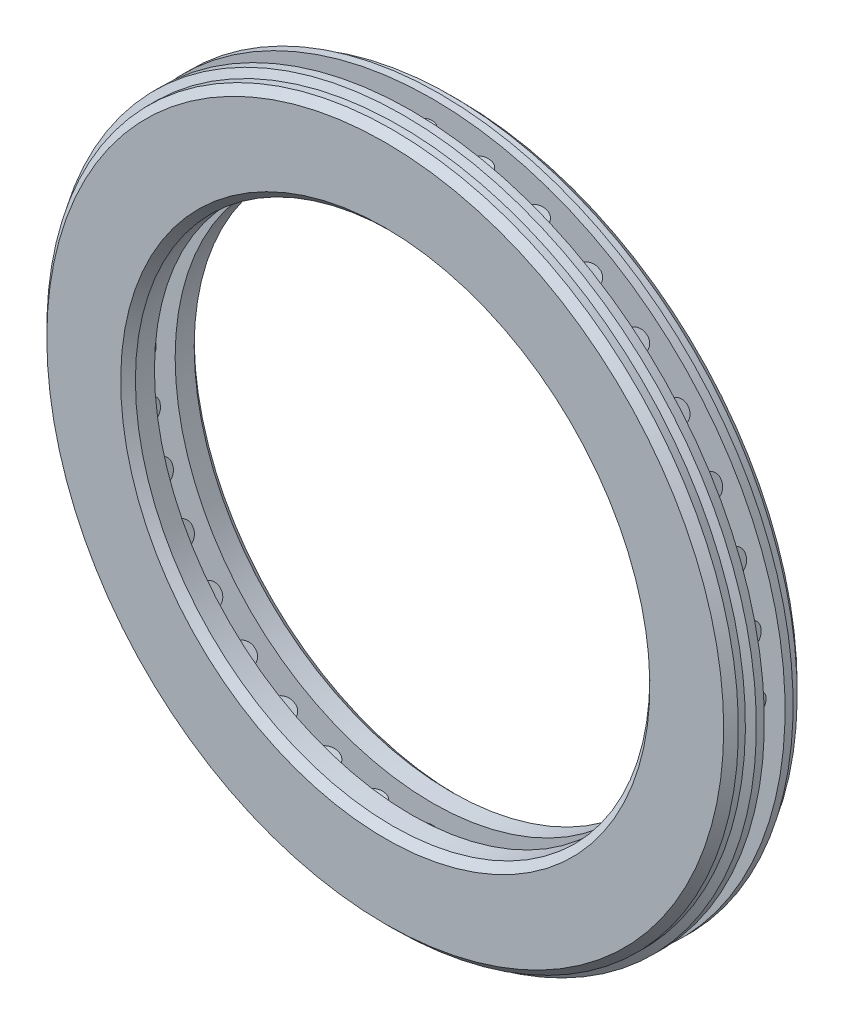
SolidWorks part; units mm, degrees
ref_plane "Front Plane" through (0, 0, 0) normal (0, 0, 1) x (1, 0, 0)
ref_plane "Top Plane" through (0, 0, 0) normal (0, 1, 0) x (1, 0, 0)
ref_plane "Right Plane" through (0, 0, 0) normal (1, 0, 0) x (0, 0, -1)
sketch "BaseSke" plane through (0, 0, 0) normal (1, 0, 0) x (0, 0, -1)
  line L0 (-47.2296, 0) -> (24.6132, 0) construction
  line L2 (0, 129.5214) -> (0, -86.3012) construction
  line L3 (-5, 48) -> (-5, 35) construction
  line L4 (-5, 48) -> (5, 48) construction
  line L5 (-5, 35) -> (5, 35) construction
  line L6 (-1.4286, 37.6) -> (0, 37.6)
  line L7 (-1.4286, 37.6) -> (-1.4286, 45.4)
  line L8 (-1.4286, 45.4) -> (0, 45.4)
  line L9 (0, 37.6) -> (0, 45.4)
  line L11 (5, 48) -> (5, 35) construction
  line L12 (-5, 41.5) -> (5, 41.5) construction
  line L13 (1.4286, 45.4) -> (1.4286, 37.6) construction
  dimension "D1" = 1.4286
  dimension "D2" = 7.8
revolve "Roller" add sketch "BaseSke" angle 360 about L2
sketch "ThrustPSke" plane through (0, 0, 0) normal (1, 0, 0) x (0, 0, -1)
  line L0 (-5, 35) -> (5, 35) construction
  line L1 (-2.5, 48) -> (-1.4086, 48)
  line L2 (-5, 47.0548) -> (-5, 35)
  line L3 (-5, 35) -> (-1.4086, 35)
  line L4 (-1.4086, 48) -> (-1.4086, 35)
  line L5 (-5, 48) -> (5, 48) construction
  line L6 (-1.4286, 37.6) -> (-1.4286, 45.4) construction
  line L7 (-5, 48) -> (-5, 35) construction
  line L8 (0, 0) -> (0, 48.3549) construction
  line L10 (-5, 47.0548) -> (-3.0457, 47.0548)
  line L11 (-2.5, 48) -> (-3.0457, 47.0548)
  line L12 (0, 129.5214) -> (0, -86.3012) construction
  line L13 (5, 35) -> (1.4086, 35)
  line L14 (1.4086, 48) -> (1.4086, 35)
  line L15 (2.5, 48) -> (1.4086, 48)
  line L16 (2.5, 48) -> (3.0457, 47.0548)
  line L17 (5, 47.0548) -> (3.0457, 47.0548)
  line L18 (5, 47.0548) -> (5, 35)
  line L19 (-10.1337, 0) -> (10.1337, 0) construction
  dimension "D1" = 0.02
  dimension "D2" = 5
  dimension "D3" = 30
revolve "ThrustPlates" add sketch "ThrustPSke" angle 360 about L19
chamfer "Chamfer1" distance 1 angle 45 4 edges at (0, -35, 5) (0, -35, -5) (0, -47.0548, 5) (0, -47.0548, -5)
pattern_circular "CirPatternBall" count 36 over 360 about axis through (0, 0, 10.1337) along (0, 0, -1) of "Roller"
sketch "SimplifiedSke" plane through (0, 0, 0) normal (1, 0, 0) x (0, 0, -1)
  line L1 (1.4286, 37.6) -> (-1.4286, 37.6)
  line L2 (1.4286, 37.6) -> (1.4286, 45.4)
  line L3 (1.4286, 45.4) -> (-1.4286, 45.4)
  line L4 (-1.4286, 37.6) -> (-1.4286, 45.4)
  line L5 (0, 0) -> (-31.7458, 0) construction
revolve "Simplified" [suppressed] add sketch "SimplifiedSke" angle 360 about L5
equation "\"D1@BaseSke\" = \"Bearing_Thickness@BaseSke\"/7"
equation "\"D2@BaseSke\" =  ( \"Bearing_Outside_Diameter@BaseSke\" - \"Bearing_Inside_Diameter@BaseSke\" )  * 0.3"
equation "\"D2@ThrustPSke\" = \"Bearing_Thickness@BaseSke\" * 0.5"
equation "\"D1@CirPatternBall\" =  int( \"Bearing_Outside_Diameter@BaseSke\" *  pi   / \"Bearing_Thickness@BaseSke\" * 1.2) "
